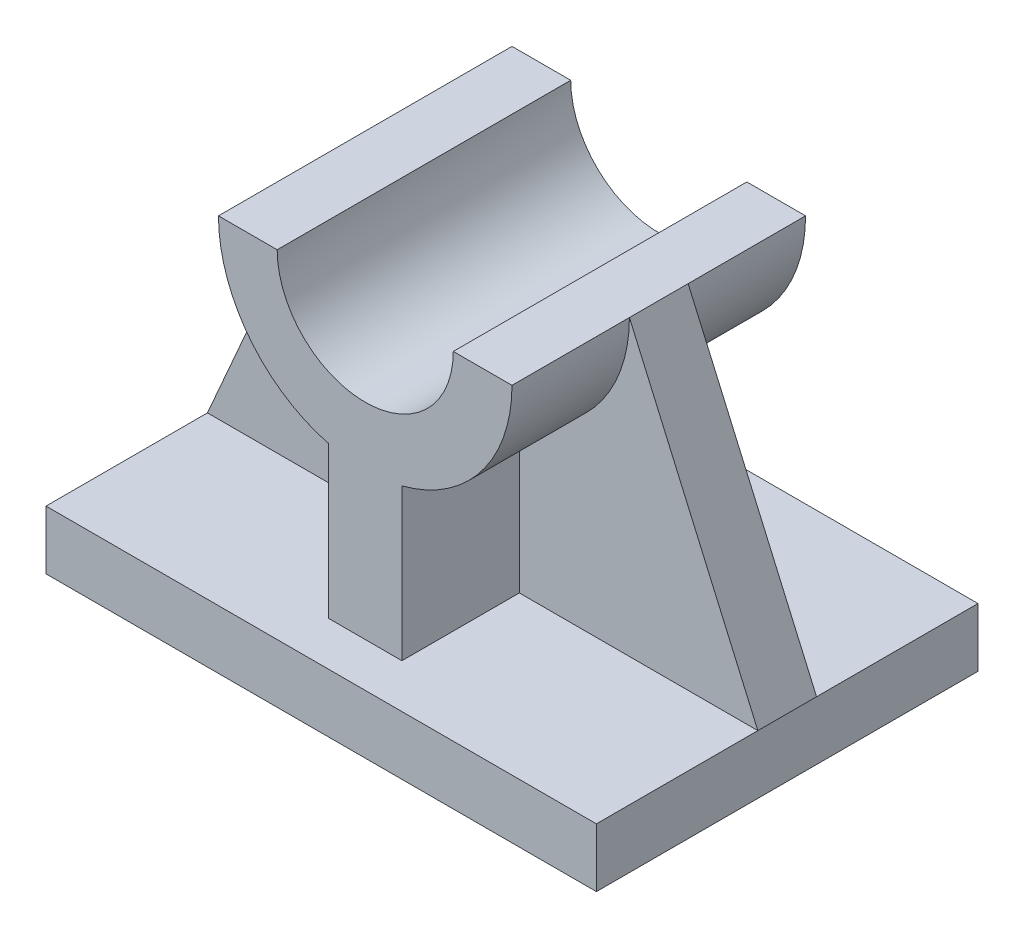
SolidWorks part; units mm, degrees
ref_plane "Front Plane" through (0, 0, 0) normal (0, 0, 1) x (1, 0, 0)
ref_plane "Top Plane" through (0, 0, 0) normal (0, 1, 0) x (1, 0, 0)
ref_plane "Right Plane" through (0, 0, 0) normal (1, 0, 0) x (0, 0, -1)
sketch "Sketch1" plane through (0, 0, 0) normal (0, 0, 1) x (1, 0, 0)
  line L0 (0, 0) -> (0, -37150.4997) construction
  line L1 (0, 0) -> (-37150.4997, 0) construction
  line L2 (-20, 0) -> (-37.5, -40)
  line L3 (-37.5, -40) -> (37.5, -40)
  line L4 (-37.5, -40) -> (-37.5, -48)
  line L5 (-37.5, -48) -> (37.5, -48)
  line L6 (-5, -19.3649) -> (-5, -40)
  line L7 (37.5, -40) -> (37.5, -48)
  line L8 (20, 0) -> (37.5, -40)
  line L9 (5, -19.3649) -> (5, -40)
  line L10 (-20, 0) -> (-12, 0)
  line L11 (12, 0) -> (20, 0)
  line L12 (-37.5, -40) -> (-37.5, -48)
  line L13 (20, 0) -> (37.5, -40)
  arc A0 (-12, 0) -> (12, 0) centre (0, 0) ccw
  arc A1 (-20, 0) -> (-5, -19.3649) centre (0, 0) ccw
  arc A2 (5, -19.3649) -> (20, 0) centre (0, 0) ccw
  point P13 (0, -40)
  point P17 (0, -48)
  dimension "D1" = 24
  dimension "D2" = 40
  dimension "D3" = 40
  dimension "D4" = 8
  dimension "D5" = 75
  dimension "D6" = 10
extrude "Boss-Extrude2" add sketch "Sketch1" along normal mid plane 52 contours L7 L3 L4 L5 region at (0, -44, 0)
extrude "Boss-Extrude4" add sketch "Sketch1<6>" along normal mid plane 40 contours L9 A2 L11 A0 L10 A1 L6 L3 region at (0, -16.9191, 0)
sketch "Sketch1<6>" plane through (0, 0, 0) normal (0, 0, 1) x (1, 0, 0) same geometry as "Sketch1"
extrude "Boss-Extrude5" add sketch "Sketch1<7>" along normal mid plane 8 contours A1 L2 L3 L6 | A2 L9 L3 L8 region at (-19.2178, -26.7367, 0) region at (19.2178, -26.7367, 0)
sketch "Sketch1<7>" plane through (0, 0, 0) normal (0, 0, 1) x (1, 0, 0) same geometry as "Sketch1"
